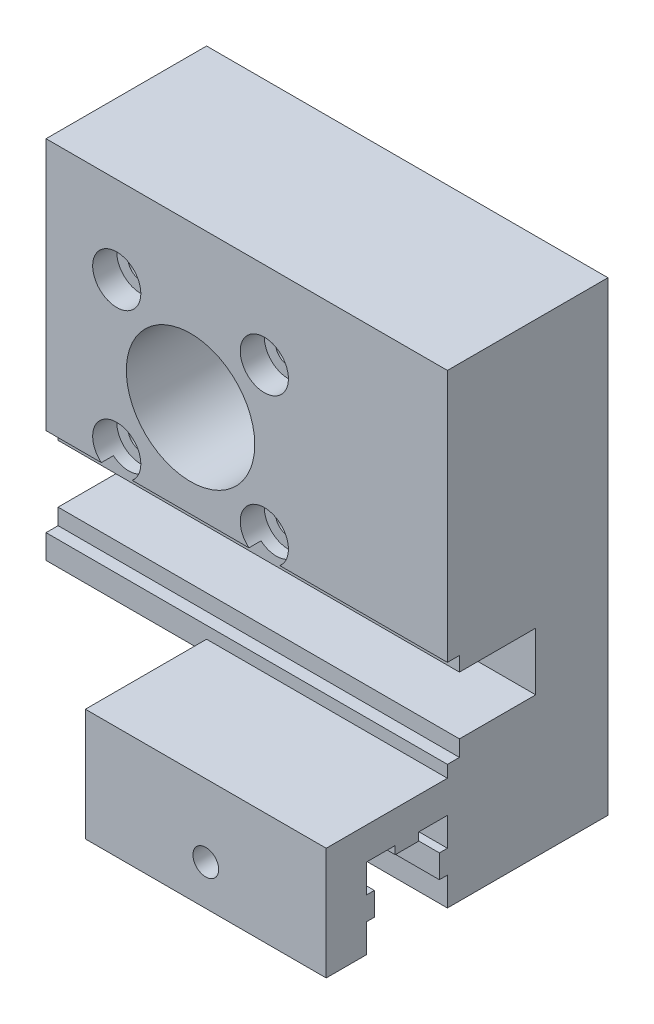
SolidWorks part; units mm, degrees
ref_plane "Front Plane" through (0, 0, 0) normal (0, 0, 1) x (1, 0, 0)
ref_plane "Top Plane" through (0, 0, 0) normal (0, 1, 0) x (1, 0, 0)
ref_plane "Right Plane" through (0, 0, 0) normal (1, 0, 0) x (0, 0, -1)
sketch "Esquisse1" plane through (0, 0, 0) normal (0, 0, 1) x (1, 0, 0)
  line L0 (25, 22.5) -> (25, -22.5)
  line L1 (-25, 22.5) -> (25, 22.5)
  line L2 (-25, 22.5) -> (-25, -22.5)
  line L3 (-25, -22.5) -> (25, -22.5)
  point P4 (-25, 0)
  point P6 (0, -22.5)
  dimension "D3" = 45
  dimension "D4" = 50
extrude "Main Extrusion" add sketch "Esquisse1" along normal blind 20
sketch "Esquisse5" plane through (0, 0, 20) normal (0, 0, 1) x (1, 0, 0)
  line L1 (-25, -22.5) -> (25, -22.5) construction
  line L3 (-25, 22.5) -> (-25, -22.5) construction
  circle A0 centre (-7, 2.5) radius 8
  dimension "D1" = 16
  dimension "D2" = 25
  dimension "D3" = 18
extrude "Gear Linear Holes" cut sketch "Esquisse5" against normal through all
sketch "Esquisse8" plane through (0, 0, 0) normal (1, 0, 0) x (0, 0, -1)
  line L0 (-20, -25.5) -> (-20, -29.05)
  line L1 (-20, -25.5) -> (-23.6, -25.5)
  line L2 (-23.6, -25.5) -> (-23.6, -26.5)
  line L3 (-23.6, -26.5) -> (-26.5, -26.5)
  line L4 (-26.5, -26.5) -> (-26.5, -25.5)
  line L5 (-35.1, -21.5) -> (0, -21.5)
  line L6 (-20, -35.5) -> (0, -35.5)
  line L7 (0, -35.5) -> (0, -21.5)
  line L8 (0, -22.5) -> (0, 22.5) construction
  line L9 (-26.5, -25.5) -> (-30.1, -25.5)
  line L10 (-20, -22.5) -> (0, -22.5) construction
  line L12 (0, 22.5) -> (0, -22.5) construction
  line L13 (-30.1, -25.5) -> (-30.1, -29.05)
  line L14 (-30.1, -35.5) -> (-35.1, -35.5)
  line L15 (-35.1, -35.5) -> (-35.1, -21.5)
  line L16 (-20, -29.05) -> (-21, -29.05)
  line L17 (-21, -29.05) -> (-21, -31.95)
  line L18 (-21, -31.95) -> (-20, -31.95)
  line L19 (-20, -31.95) -> (-20, -35.5)
  line L21 (-30.1, -29.05) -> (-29.1, -29.05)
  line L22 (-29.1, -29.05) -> (-29.1, -31.95)
  line L23 (-29.1, -31.95) -> (-30.1, -31.95)
  line L24 (-30.1, -31.95) -> (-30.1, -35.5)
  line L25 (-20, 22.5) -> (-20, -22.5) construction
  dimension "D1" = 2.9
  dimension "D2" = 10.1
  dimension "D3" = 1
  dimension "D4" = 3
  dimension "D5" = 10
  dimension "D6" = 5
  dimension "D7" = 4
extrude "Fixing Extrusion" add sketch "Esquisse8" along normal mid plane 50
sketch "Esquisse12" plane through (0, 0, 0) normal (0, 0, 1) x (1, 0, 0)
  circle A0 centre (-7, 2.5) radius 16
  dimension "D1" = 32
sketch "Esquisse13" plane through (0, 0, 20) normal (0, 0, 1) x (1, 0, 0)
  line L0 (-25, 22.5) -> (-25, -21.5) construction
  line L1 (-25, -18) -> (25, -18)
  line L2 (-25, -18) -> (-25, -10.8)
  line L3 (-25, -10.8) -> (25, -10.8)
  line L4 (25, -18) -> (25, -10.8)
  line L5 (25, -21.5) -> (25, 22.5) construction
  line L7 (-25, -21.5) -> (25, -21.5) construction
  dimension "D1" = 3.5
  dimension "D2" = 7.2
extrude "RollingBallHorizontalHole" cut sketch "Esquisse13" against normal blind 11
sketch "Esquisse14" plane through (-25, 0, 0) normal (-1, 0, 0) x (0, 0, 1)
  line L0 (0, -23) -> (20, -23)
  line L1 (0, -35.5) -> (35.1, -35.5)
  line L2 (0, -35.5) -> (0, -23)
  line L3 (20, -23) -> (20, -18)
  line L4 (35.1, -35.5) -> (35.1, -18)
  line L5 (20, -18) -> (35.1, -18)
  line L6 (20, -18) -> (20, -21.5) construction
  dimension "D1" = 12.5
extrude "FrontHole" cut sketch "Esquisse14" against normal blind 20
sketch "Esquisse15" plane through (0, 0, 35.1) normal (0, 0, 1) x (1, 0, 0)
  line L1 (25, -21.5) -> (25, -35.5) construction
  line L4 (-5, -31.95) -> (-5, -29.05) construction
  circle A1 centre (10, -30.5) radius 1.6
  point P5 (-5, -30.5)
  dimension "D1" = 3.2
  dimension "D2" = 15
extrude "BottomFixingHole" cut sketch "Esquisse15" against normal through all
extrude "ReductorMainHole" cut sketch "Esquisse12" along normal blind 5
sketch "Esquisse16" plane through (0, 0, 5) normal (0, 0, -1) x (-1, 0, 0)
  line L0 (2.6411, 11.5) -> (11.3589, 11.5)
  line L1 (2.6411, -6.5) -> (11.3589, -6.5)
  arc A0 (2.6411, 11.5) -> (2.6411, -6.5) centre (7, 2.5) ccw
  arc A2 (11.3589, 11.5) -> (11.3589, -6.5) centre (7, 2.5) cw
  circle A3 centre (7, 2.5) radius 16 construction
  dimension "D1" = 10
  dimension "D2" = 18
extrude "ReductorFrontFixingHole" cut sketch "Esquisse16" against normal blind 3
sketch "Esquisse17" plane through (0, 0, 5) normal (0, 0, -1) x (-1, 0, 0)
  line L0 (7, 2.5) -> (-2.1924, 11.6924) construction
  line L1 (19.305, 0) -> (-19.305, 0) construction
  line L2 (-2.1924, -6.6924) -> (16.1924, 11.6924) construction
  line L3 (7, 2.5) -> (16.1924, -6.6924) construction
  circle A0 centre (-2.1924, 11.6924) radius 1.6
  circle A1 centre (16.1924, 11.6924) radius 1.6
  circle A2 centre (-2.1924, -6.6924) radius 1.6
  circle A3 centre (16.1924, -6.6924) radius 1.6
  dimension "D1" = 3.2
  dimension "D2" = 45
  dimension "D3" = 13
  dimension "D4" = 13
  dimension "D5" = 13
extrude "MotorFixingHole" cut sketch "Esquisse17" against normal through all
sketch "Esquisse19" plane through (0, 0, 20) normal (0, 0, 1) x (1, 0, 0)
  circle A0 centre (-16.1924, 11.6924) radius 3
  circle A1 centre (2.1924, 11.6924) radius 3
  circle A2 centre (-16.1924, -6.6924) radius 3
  circle A3 centre (2.1924, -6.6924) radius 3
  dimension "D1" = 6
extrude "Enlèv. mat.-Extru.5" cut sketch "Esquisse19" against normal blind 3
sketch "Sketch2" plane through (25, 0, 0) normal (1, 0, 0) x (0, 0, -1)
  line L1 (-20, -20) -> (-18.5, -20)
  line L2 (-20, -20) -> (-20, -9)
  line L3 (-20, -9) -> (-18.5, -9)
  line L4 (-18.5, -20) -> (-18.5, -9)
  line L6 (-9, -18) -> (-20, -18) construction
  line L7 (-20, -10.8) -> (-20, 22.5) construction
  point P6 (-16.7147, -9)
  dimension "D1" = 11
  dimension "D2" = 1.5
  dimension "D3" = 2
extrude "CutForMakerBeamProfile" cut sketch "Sketch2" against normal through all
ref_plane "Plane1" through (0, 0, -5) normal (0, 0, 1) x (1, 0, 0)
